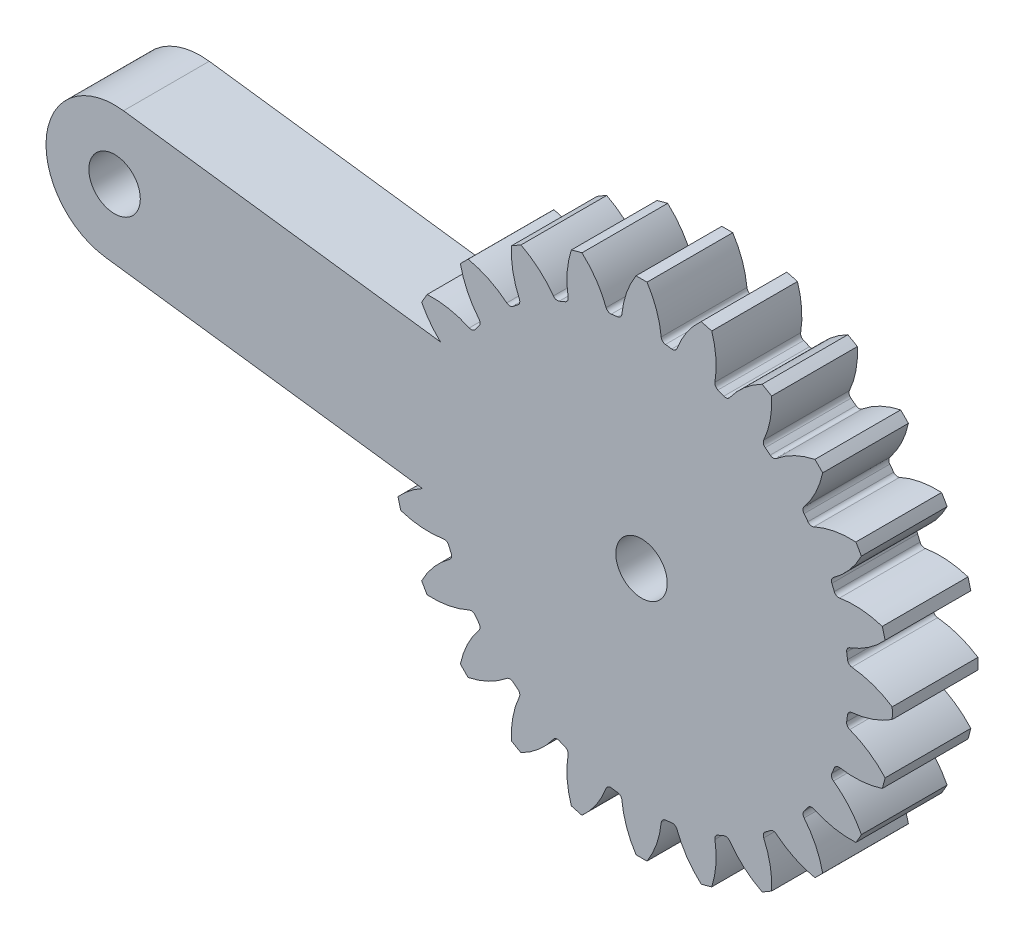
SolidWorks part; units mm, degrees
material "아크릴(내충격성)"
ref_plane "정면" through (0, 0, 0) normal (0, 0, 1) x (1, 0, 0)
ref_plane "윗면" through (0, 0, 0) normal (0, 1, 0) x (1, 0, 0)
ref_plane "우측면" through (0, 0, 0) normal (1, 0, 0) x (0, 0, -1)
sketch "스케치1" plane through (0, 0, 0) normal (0, 0, 1) x (1, 0, 0)
  line L0 (0, 17.8552) -> (0, -21.2428) construction
  line L1 (0.8831, 13.4711) -> (0.8831, -21.2428) construction
  line L2 (0.3206, 14.6215) -> (0.3206, -21.2428) construction
  line L3 (1.1644, 12.0376) -> (1.1644, -21.2428) construction
  line L4 (1.1644, 17.8552) -> (1.1644, -21.2428) construction
  line L5 (0.8831, 17.8552) -> (0.8831, -21.2428) construction
  line L6 (0.3206, 17.8552) -> (0.3206, -21.2428) construction
  circle A0 centre (0, 0) radius 13.5 construction
  circle A1 centre (0, 0) radius 14.625
  circle A2 centre (0, 0) radius 12.0938
  arc A3 (1.1644, 12.0376) -> (0.3206, 14.6215) centre (-4.0938, 11.7503) ccw
  arc A4 (-1.1644, 12.0376) -> (-0.3206, 14.6215) centre (4.0938, 11.7503) cw
  circle A5 centre (0, 0) radius 1.5
  point P17 (-0.8831, 13.4711)
  dimension "D1" = 27
  dimension "D2" = 29.25
  dimension "D3" = 24.1875
  dimension "D7" = 3
  dimension "D6" = 0.2812
  dimension "D4" = 0.8831
  dimension "D5" = 0.5625
extrude "보스-돌출2" add sketch "스케치1" along normal blind 5 contours A2 A3 region at (8.7005, 7.8996, 0)
extrude "보스-돌출3" add sketch "스케치1<4>" along normal blind 5 contours A4 A2 A3 A1 region at (0, 13.145, 0)
sketch "스케치1<4>" plane through (0, 0, 0) normal (0, 0, 1) x (1, 0, 0) same geometry as "스케치1"
fillet "필렛2" radius 0.2812 2 edges at (-1.1644, 12.0376, 2.5) (1.1644, 12.0376, 2.5)
pattern_circular "원형 패턴1" count 24 over 360 about axis through (0, 0, 5) along (0, 0, -1) of "보스-돌출3", "필렛2" reverse direction yes
sketch "스케치2" plane through (0, 0, 5) normal (0, 0, 1) x (1, 0, 0)
  line L0 (0, 0) -> (-30.7348, 4.0463) construction
  line L1 (-0.5221, -3.9658) -> (-31.2569, 0.0805)
  line L2 (0.5221, 3.9658) -> (-30.2127, 8.0121)
  line L3 (22.211, 0) -> (-40.8343, 0) construction
  arc A0 (-0.5221, -3.9658) -> (0.5221, 3.9658) centre (0, 0) ccw
  arc A1 (-30.2127, 8.0121) -> (-31.2569, 0.0805) centre (-30.7348, 4.0463) ccw
  circle A2 centre (-30.7348, 4.0463) radius 1.5
  circle A4 centre (0, 0) radius 1.5 construction
  circle A5 centre (0, 0) radius 1.5
  point P3 (-15.3674, 2.0232)
  dimension "D2" = 3
  dimension "D4" = 7.5
  dimension "D1" = 31
  dimension "D3" = 8
extrude "보스-돌출4" add sketch "스케치2" against normal up to surface (5 mm away) contours L2 A1 L1 A0 A5 A2 | L2 A1 L1 A0 | A2 | A5 region at (-15.3674, 2.0232, 5) up to face at (1.5, 0, 0)
